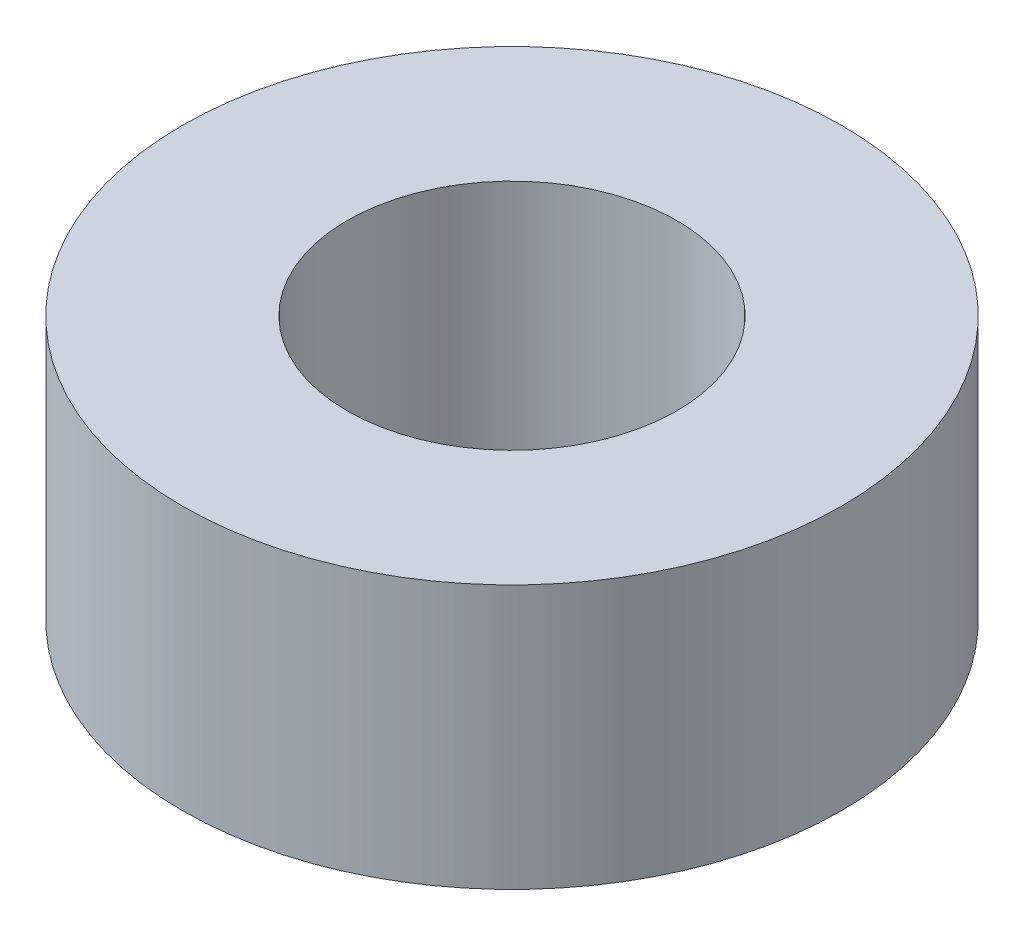
SolidWorks part; units mm, degrees
ref_plane "Płaszczyzna przednia" through (0, 0, 0) normal (0, 0, 1) x (1, 0, 0)
ref_plane "Płaszczyzna górna" through (0, 0, 0) normal (0, 1, 0) x (1, 0, 0)
ref_plane "Płaszczyzna prawa" through (0, 0, 0) normal (1, 0, 0) x (0, 0, -1)
sketch "Szkic1" plane through (0, 0, 0) normal (0, 1, 0) x (1, 0, 0)
  circle A0 centre (0, 0) radius 5
  circle A1 centre (0, 0) radius 2.5
  dimension "D1" = 10
  dimension "D2" = 5
extrude "Dodanie-wyciągnięcie1" add sketch "Szkic1" along normal blind 4
